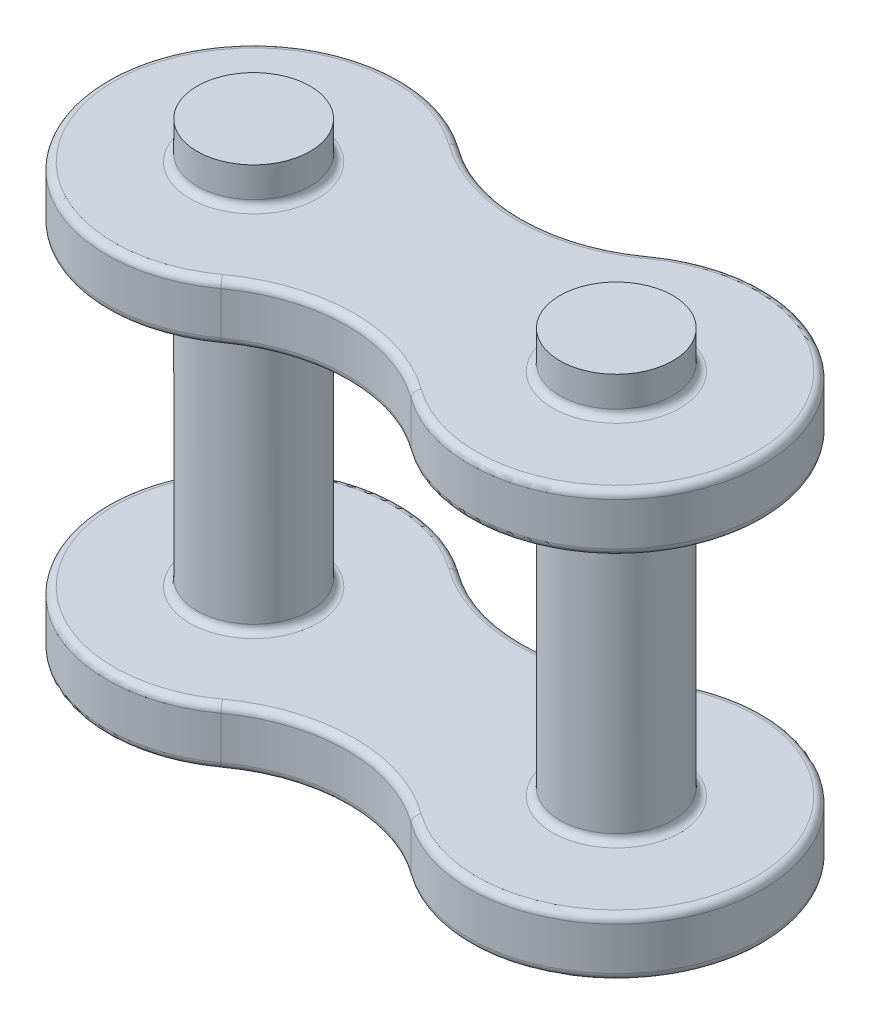
SolidWorks part; units mm, degrees
material "Alloy Steel"
ref_plane "X-Y Datum" through (0, 0, 0) normal (0, 0, 1) x (1, 0, 0)
ref_plane "X-Z Datum" through (0, 0, 0) normal (0, 1, 0) x (1, 0, 0)
ref_plane "Y-Z Datum" through (0, 0, 0) normal (1, 0, 0) x (0, 0, -1)
sketch "Sketch2" plane through (0, 0, 0) normal (0, 1, 0) x (1, 0, 0)
  line L0 (0, -9.7123) -> (0, 9.7123) construction
  line L1 (12.7033, 0) -> (-12.7033, 0) construction
  circle A0 centre (-6.35, 0) radius 1.98
  arc A1 (-3.3293, 4.163) -> (-3.3293, -4.163) centre (-6.35, 0) ccw
  circle A2 centre (6.35, 0) radius 1.98
  arc A3 (3.3293, 4.163) -> (3.3293, -4.163) centre (6.35, 0) cw
  arc A4 (-3.3293, 4.163) -> (3.3293, 4.163) centre (0, 8.7513) ccw
  arc A5 (-3.3293, -4.163) -> (3.3293, -4.163) centre (0, -8.7513) cw
  point P4 (0, 0)
  point P8 (0, 0)
  dimension "D1" = 10.287
  dimension "D2" = 3.96
  dimension "D3" = 6.35
extrude "Boss-Extrude1" add sketch "Sketch2" along normal mid plane 2.0066
ref_plane "Center Plane" through (0, 6.4389, 0) normal (0, 1, 0) x (1, 0, 0)
sketch "Sketch5" plane through (0, 6.4389, 0) normal (0, 1, 0) x (1, 0, 0)
  line L0 (0, -55) -> (0, 55) construction
  circle A0 centre (-6.35, 0) radius 1.98 construction
  circle A1 centre (-6.35, 0) radius 1.98
  circle A2 centre (6.35, 0) radius 1.98
extrude "Boss-Extrude2" add sketch "Sketch5" along normal mid plane 17.5006
fillet "Fillet1" radius 0.254 12 edges at (11.4935, -1.0033, 0) (0, -1.0033, 3.0824) (-11.4935, -1.0033, 0) (0, 1.0033, -3.0824) (11.4935, 1.0033, 0) (0, 1.0033, 3.0824) (-6.35, -1.0033, 1.98) (6.35, -1.0033, 1.98) (6.35, 1.0033, -1.98) (-6.35, 1.0033, 1.98) (0, -1.0033, -3.0824) (-11.4935, 1.0033, 0)
mirror "Mirror1" about plane through (0, 6.4389, 0) normal (0, 1, 0) of "Fillet1", "Boss-Extrude1"
ref_plane "Plane1" through (0, 6.4389, 0) normal (0, 1, 0) x (1, 0, 0)
ref_plane "Plane2" through (0, 6.4389, 0) normal (0, 1, 0) x (1, 0, 0)
